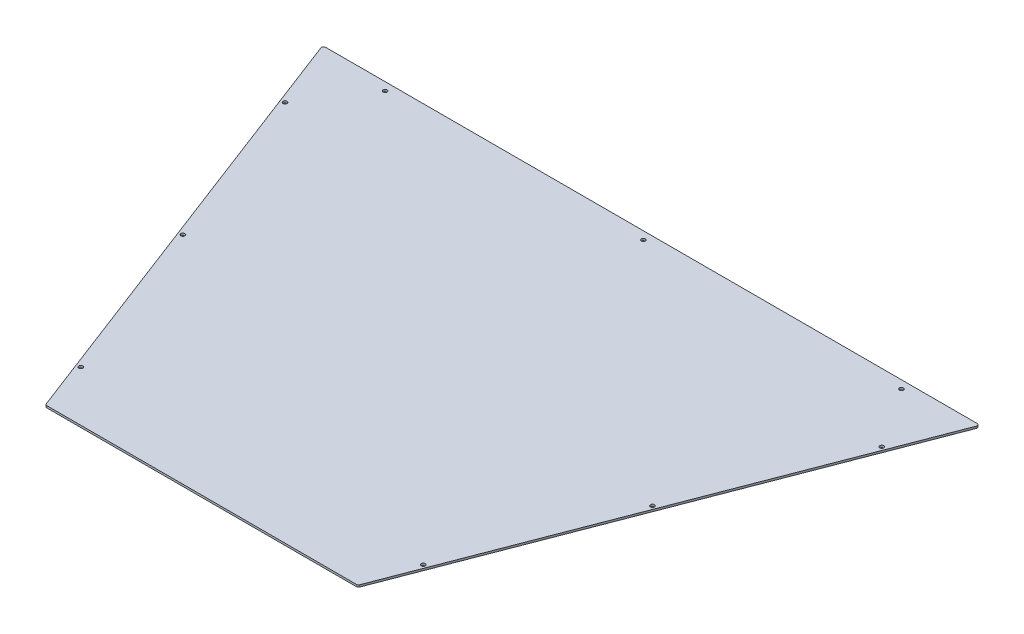
SolidWorks part; units mm, degrees
material "PE High Density"
ref_plane "Front Plane" through (0, 0, 0) normal (0, 0, 1) x (1, 0, 0)
ref_plane "Top Plane" through (0, 0, 0) normal (0, 1, 0) x (1, 0, 0)
ref_plane "Right Plane" through (0, 0, 0) normal (1, 0, 0) x (0, 0, -1)
sketch "Sketch1" plane through (0, 0, 0) normal (0, 1, 0) x (1, 0, 0)
  line L0 (-245.912, 0) -> (245.912, 0)
  line L1 (245.912, 0) -> (517.525, 708.025)
  line L2 (517.525, 708.025) -> (-517.525, 708.025)
  line L3 (-517.525, 708.025) -> (-245.912, 0)
  dimension "D1" = 1035.05
  dimension "D2" = 69.012
  dimension "D3" = 708.025
extrude "Boss-Extrude1" add sketch "Sketch1" along normal blind 3.175
fillet "Fillet1" radius 3.175 4 edges at (517.525, 1.5875, -708.025) (-517.525, 1.5875, -708.025) (-245.912, 1.5875, 0) (245.912, 1.5875, 0)
sketch "Sketch2" plane through (0, 3.175, 0) normal (0, 1, 0) x (1, 0, 0)
  line L0 (512.9064, 708.025) -> (-512.9064, 708.025) construction
  line L1 (-469.6817, 601.0389) -> (-269.5364, 79.3117) construction
  line L2 (469.6817, 601.0389) -> (269.5364, 79.3117) construction
  line L3 (-515.8708, 703.7128) -> (-246.6937, 2.0378) construction
  line L4 (246.6937, 2.0378) -> (515.8708, 703.7128) construction
  point P0 (0, 695.325)
  point P1 (-406.4, 695.325)
  point P2 (406.4, 695.325)
  point P5 (0, 708.025)
  point P6 (-469.6817, 601.0389)
  point P7 (-369.609, 340.1753)
  point P8 (-269.5364, 79.3117)
  point P9 (269.5364, 79.3117)
  point P10 (369.609, 340.1753)
  point P11 (469.6817, 601.0389)
  point P16 (-371.2307, 347.5775)
  point P23 (-381.2822, 352.8753)
  dimension "D1" = 12.7
  dimension "D2" = 406.4
  dimension "D3" = 406.4
  dimension "D4" = 6.35
  dimension "D5" = 6.35
  dimension "D6" = 558.8
  dimension "D7" = 12.7
hole_wizard "1/4 (0.25) Diameter Hole1" positions "Sketch3" profile "Sketch4" hole size "1/4" standard "ANSI Inch" end condition through all
sketch "Sketch3" plane through (0, 3.175, 0) normal (0, 1, 0) x (1, 0, 0)
  line L0 (469.6817, 601.0389) -> (269.5364, 79.3117) construction
  point P0 (-406.4, 695.325)
  point P3 (0, 695.325)
  point P6 (406.4, 695.325)
  point P9 (-469.6817, 601.0389)
  point P12 (-369.609, 340.1753)
  point P15 (-269.5364, 79.3117)
  point P18 (269.5364, 79.3117)
  point P23 (369.609, 340.1753)
  point P27 (469.6817, 601.0389)
sketch "Sketch4" plane through (-406.4, 3.175, -695.325) normal (1, 0, 0) x (0, 0, 1)
  line L0 (0, 0) -> (0, 3.175)
  line L1 (0, 3.175) -> (3.175, 3.175)
  line L2 (3.175, 3.175) -> (3.175, 0)
  line L5 (3.175, 0) -> (0, 0)
  line L11 (0, -6.35) -> (0, 107.95) construction
  dimension "Thru Hole Dia." = 6.35
  dimension "Thru Hole Depth" = 3.175
equation "\"D3@Sketch2\"=\"D2@Sketch2\""
